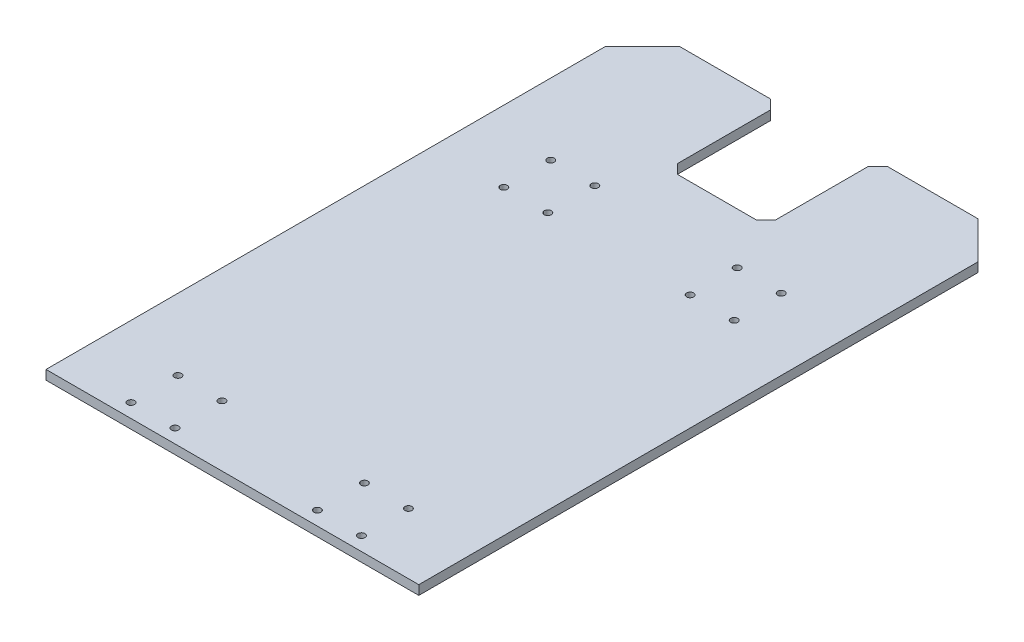
SolidWorks part; units mm, degrees
ref_plane "Front Plane" through (0, 0, 0) normal (0, 0, 1) x (1, 0, 0)
ref_plane "Top Plane" through (0, 0, 0) normal (0, 1, 0) x (1, 0, 0)
ref_plane "Right Plane" through (0, 0, 0) normal (1, 0, 0) x (0, 0, -1)
sketch "Sketch2" plane through (0, 0, 0) normal (0, 1, 0) x (1, 0, 0)
  line L1 (-127, 152.4) -> (127, 152.4)
  line L2 (-127, 152.4) -> (-127, -152.4)
  line L3 (-127, -152.4) -> (127, -152.4)
  line L4 (127, 152.4) -> (127, -152.4)
  line L5 (-127, 152.4) -> (127, -152.4) construction
  line L6 (-127, -152.4) -> (127, 152.4) construction
  point P0 (0, 0)
  dimension "D1" = 304.8
  dimension "D2" = 254
extrude "Boss-Extrude1" add sketch "Sketch2" along normal blind 6.35
ref_plane "Top" through (0, 0, -152.4) normal (0, 0, -1) x (-1, 0, 0)
hole_wizard "M4 Clearance Hole1" positions "Sketch4" profile "Sketch5" hole size "M4" standard "ANSI Metric" end condition up to next
sketch "Sketch4" plane through (0, 6.35, 0) normal (0, 1, 0) x (1, 0, 0)
  circle A0 centre (78.5, -111) radius 2.5 construction
  circle A1 centre (48.5, -111) radius 2.5 construction
  circle A2 centre (48.5, -143) radius 2.5 construction
  circle A3 centre (78.5, -143) radius 2.5 construction
  circle A4 centre (-48.5, -111) radius 2.5 construction
  circle A5 centre (-48.5, -143) radius 2.5 construction
  circle A6 centre (-78.5, -111) radius 2.5 construction
  circle A7 centre (-78.5, -143) radius 2.5 construction
  circle A8 centre (78.5, 143) radius 2.5 construction
  circle A9 centre (78.5, 111) radius 2.5 construction
  circle A10 centre (48.5, 143) radius 2.5 construction
  circle A11 centre (48.5, 111) radius 2.5 construction
  circle A12 centre (-48.5, 143) radius 2.5 construction
  circle A13 centre (-48.5, 111) radius 2.5 construction
  circle A14 centre (-78.5, 143) radius 2.5 construction
  circle A15 centre (-78.5, 111) radius 2.5 construction
  circle A16 centre (78.5, -111) radius 2.5 construction
  circle A17 centre (48.5, -111) radius 2.5 construction
  circle A18 centre (48.5, -143) radius 2.5 construction
  circle A19 centre (78.5, -143) radius 2.5 construction
  circle A20 centre (-48.5, -111) radius 2.5 construction
  circle A21 centre (-48.5, -143) radius 2.5 construction
  circle A22 centre (-78.5, -111) radius 2.5 construction
  circle A23 centre (-78.5, -143) radius 2.5 construction
  circle A24 centre (78.5, 143) radius 2.5 construction
  circle A25 centre (78.5, 111) radius 2.5 construction
  circle A26 centre (48.5, 143) radius 2.5 construction
  circle A27 centre (48.5, 111) radius 2.5 construction
  circle A28 centre (-48.5, 143) radius 2.5 construction
  circle A29 centre (-48.5, 111) radius 2.5 construction
  circle A30 centre (-78.5, 143) radius 2.5 construction
  circle A31 centre (-78.5, 111) radius 2.5 construction
  point P1 (78.5, -111)
  point P3 (48.5, -111)
  point P5 (48.5, -143)
  point P7 (78.5, -143)
  point P9 (-48.5, -111)
  point P11 (-48.5, -143)
  point P13 (-78.5, -111)
  point P15 (-78.5, -143)
  point P17 (78.5, 143)
  point P19 (78.5, 111)
  point P21 (48.5, 143)
  point P23 (48.5, 111)
  point P25 (-48.5, 143)
  point P27 (-48.5, 111)
  point P29 (-78.5, 143)
  point P31 (-78.5, 111)
sketch "Sketch5" plane through (78.5, 6.35, 111) normal (1, 0, 0) x (0, 0, 1)
  line L0 (0, 0) -> (0, 6.35)
  line L1 (0, 6.35) -> (2.4, 6.35)
  line L2 (2.4, 6.35) -> (2.4, 0)
  line L5 (2.4, 0) -> (0, 0)
  line L11 (0, -6.35) -> (0, 107.95) construction
  dimension "Thru Hole Dia." = 4.8
  dimension "Thru Hole Depth" = 6.35
sketch "Sketch6" plane through (0, 0, -152.4) normal (0, 0, -1) x (-1, 0, 0)
  line L4 (-127, 0) -> (127, 0)
  line L5 (127, 0) -> (127, 6.35)
  line L6 (127, 6.35) -> (-127, 6.35)
  line L7 (-127, 6.35) -> (-127, 0)
  line L8 (-127, 0) -> (127, 0)
  line L9 (127, 0) -> (127, 6.35)
  line L10 (127, 6.35) -> (-127, 6.35)
  line L11 (-127, 6.35) -> (-127, 0)
  dimension "D1" = 0
extrude "Boss-Extrude2" add sketch "Sketch6" along normal blind 101.6
chamfer "Chamfer1" distance 25.4 angle 45 2 edges at (-127, 3.175, -254) (127, 3.175, -254)
sketch "Sketch7" plane through (0, 6.35, 0) normal (0, 1, 0) x (1, 0, 0)
  line L0 (-101.6, 254) -> (101.6, 254) construction
  line L1 (-33.3375, 254) -> (33.3375, 254)
  line L2 (-33.3375, 254) -> (-33.3375, 177.8)
  line L3 (-33.3375, 177.8) -> (33.3375, 177.8)
  line L4 (33.3375, 254) -> (33.3375, 177.8)
  line L5 (-33.3375, 254) -> (33.3375, 177.8) construction
  line L6 (-33.3375, 177.8) -> (33.3375, 254) construction
  line L7 (-101.6, 254) -> (101.6, 254) construction
  point P0 (0, 215.9)
  point P7 (0, 0)
  point P9 (0, 254)
  dimension "D1" = 66.675
  dimension "D2" = 76.2
extrude "Cut-Extrude1" cut sketch "Sketch7" against normal through all
chamfer "Chamfer2" distance 6.35 angle 45 4 edges at (33.3375, 3.175, -177.8) (-33.3375, 3.175, -177.8) (33.3375, 3.175, -254) (-33.3375, 3.175, -254)
